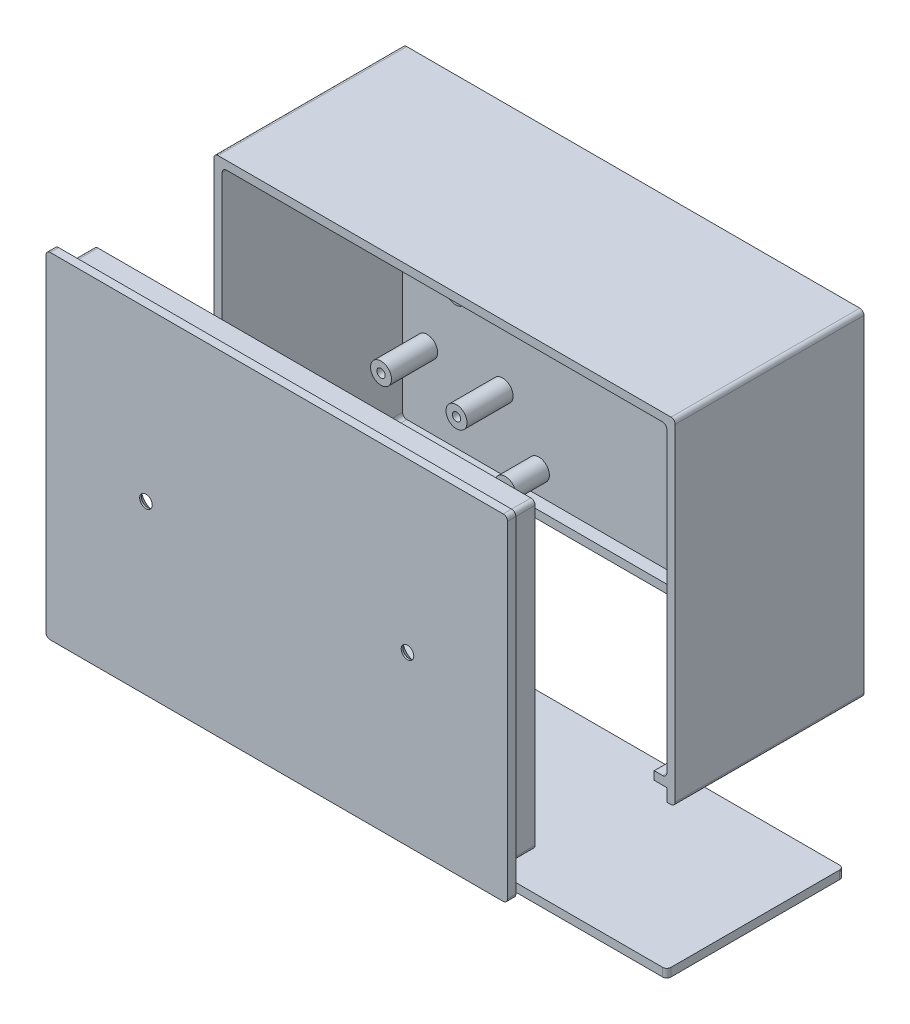
SolidWorks part; units mm, degrees
ref_plane "Спереди" through (0, 0, 0) normal (0, 0, 1) x (1, 0, 0)
ref_plane "Сверху" through (0, 0, 0) normal (0, 1, 0) x (1, 0, 0)
ref_plane "Справа" through (0, 0, 0) normal (1, 0, 0) x (0, 0, -1)
sketch "Эскиз1" plane through (0, 0, 0) normal (0, 0, 1) x (1, 0, 0)
  line L0 (-55, -41.511) -> (-53, -41.511)
  line L2 (-55, 38.489) -> (-55, -41.511)
  line L5 (-55, 38.489) -> (55, 38.489)
  line L6 (53, -36.511) -> (53, 36.489)
  line L7 (-53, -41.511) -> (-53, -38.511)
  line L8 (-53, -38.511) -> (-50, -38.511)
  line L9 (-50, -38.511) -> (-50, -36.511)
  line L10 (-50, -36.511) -> (-53, -36.511)
  line L11 (-53, -36.511) -> (-53, 36.489)
  line L12 (-53, 36.489) -> (53, 36.489)
  line L13 (0, 55.7111) -> (0, -96.3987) construction
  line L14 (50, -36.511) -> (53, -36.511)
  line L15 (50, -38.511) -> (50, -36.511)
  line L16 (53, -38.511) -> (50, -38.511)
  line L17 (53, -41.511) -> (53, -38.511)
  line L18 (55, 38.489) -> (55, -41.511)
  line L19 (55, -41.511) -> (53, -41.511)
  point P0 (0, 0)
  point P15 (0, 36.489)
  point P21 (0, 38.489)
  dimension "D1" = 2
  dimension "D2" = 2
  dimension "D3" = 2
  dimension "D4" = 55
  dimension "D5" = 80
  dimension "D6" = 2
  dimension "D7" = 3
  dimension "D8" = 3
extrude "Бобышка-Вытянуть3" add sketch "Эскиз1" along normal blind 43
sketch "Эскиз2" plane through (0, 0, 0) normal (0, 0, -1) x (-1, 0, 0)
  line L36 (55, 38.489) -> (55, -41.511) construction
  line L37 (-55, 38.489) -> (55, 38.489) construction
  line L38 (-55, -41.511) -> (-55, 38.489) construction
  line L39 (55, 38.489) -> (55, -41.511)
  line L40 (-55, 38.489) -> (55, 38.489)
  line L41 (-55, -41.511) -> (-55, 38.489)
  line L42 (-55, -41.511) -> (55, -41.511)
extrude "Бобышка-Вытянуть4" add sketch "Эскиз2" along normal blind 2
ref_plane "Плоскость1" through (0, 0, 8) normal (0, 0, 1) x (1, 0, 0)
sketch "Эскиз3" plane through (0, 0, 8) normal (0, 0, 1) x (1, 0, 0)
  line L0 (-53, -38.511) -> (-50, -38.511) construction
  line L1 (48, -32.511) -> (-23, -32.511) construction
  line L2 (48, -32.511) -> (48, 17.489) construction
  line L3 (48, 17.489) -> (-23, 17.489) construction
  line L4 (-23, -32.511) -> (-23, 17.489) construction
  line L5 (-33.1063, -7.511) -> (53.7568, -7.511) construction
  line L6 (12.5, 27.0434) -> (12.5, -35.2357) construction
  line L8 (50, -38.511) -> (53, -38.511) construction
  line L9 (53, 36.489) -> (53, -36.511) construction
  line L10 (-38.1409, 10.489) -> (-38.1409, -27.511) construction
  line L11 (-49.1409, 10.489) -> (-27.1409, 10.489) construction
  line L12 (-49.1409, 10.489) -> (-49.1409, -27.511) construction
  line L13 (-49.1409, -27.511) -> (-27.1409, -27.511) construction
  line L14 (-27.1409, 10.489) -> (-27.1409, -27.511) construction
  circle A0 centre (-20.5, 15.989) radius 1
  circle A1 centre (-20.5, 15.989) radius 2.5
  circle A2 centre (45.5, 15.989) radius 2.5
  circle A3 centre (45.5, 15.989) radius 1
  circle A4 centre (-20.5, 15.989) radius 1
  circle A5 centre (-20.5, 15.989) radius 2.5
  circle A6 centre (45.5, 15.989) radius 2.5
  circle A7 centre (45.5, 15.989) radius 1
  circle A8 centre (45.5, -31.011) radius 1
  circle A9 centre (45.5, -31.011) radius 2.5
  circle A10 centre (-20.5, -31.011) radius 2.5
  circle A11 centre (-20.5, -31.011) radius 1
  circle A12 centre (45.5, -31.011) radius 1
  circle A13 centre (45.5, -31.011) radius 2.5
  circle A14 centre (-20.5, -31.011) radius 2.5
  circle A15 centre (-20.5, -31.011) radius 1
  circle A16 centre (-47.1409, -19.011) radius 1
  circle A17 centre (-47.1409, -19.011) radius 2.5
  circle A18 centre (-29.1409, -19.011) radius 2.5
  circle A19 centre (-29.1409, -19.011) radius 1
  circle A20 centre (-29.3409, 6.489) radius 2.5
  circle A21 centre (-29.3409, 6.489) radius 1
  point P0 (12.5, -7.511)
  point P35 (12.5, 17.489)
  point P36 (-23, -7.511)
  point P40 (-38.1409, -8.8408)
  point P51 (0, 0)
  point P52 (0, 0)
  point P53 (-27.3853, 3.4956)
  point P54 (0, 0)
  point P55 (0, 0)
  point P56 (0, 0)
  point P57 (0, 0)
  point P59 (0, 0)
  dimension "D5" = 2
  dimension "D6" = 5
  dimension "D11" = 2
  dimension "D12" = 5
  dimension "D1" = 50
  dimension "D2" = 71
  dimension "D3" = 6
  dimension "D4" = 5
  dimension "D7" = 47
  dimension "D8" = 66
  dimension "D9" = 38
  dimension "D10" = 22
  dimension "D13" = 8.5
  dimension "D14" = 18
  dimension "D15" = 4
  dimension "D16" = 2.2
  dimension "D17" = 11
extrude "Бобышка-Вытянуть2" add sketch "Эскиз3" against normal up to surface (8 mm away) contours A1 | A10 | A11 | A2 | A3 | A9 | A8 | A0 up to face at (0, -25.8443, 0)
sketch "Эскиз4" plane through (0, 0, 0) normal (0, 0, 1) x (1, 0, 0)
  line L0 (-50, -36.511) -> (-50, -38.511)
  line L1 (-50, -38.511) -> (50, -38.511)
  line L2 (50, -38.511) -> (50, -36.511)
  line L3 (50, -36.511) -> (-50, -36.511)
extrude "Бобышка-Вытянуть5" add sketch "Эскиз4" along normal blind 3
ref_plane "Плоскость2" through (0, 0, 83) normal (0, 0, 1) x (1, 0, 0)
sketch "Эскиз5" plane through (0, 0, 83) normal (0, 0, 1) x (1, 0, 0)
  line L0 (55, -41.511) -> (55, 38.489) construction
  line L1 (55, 38.489) -> (-55, 38.489) construction
  line L2 (-55, 38.489) -> (-55, -41.511) construction
  line L3 (55, -41.511) -> (55, 38.489)
  line L4 (55, 38.489) -> (-55, 38.489)
  line L5 (-55, 38.489) -> (-55, -41.511)
  line L6 (-55, -41.511) -> (55, -41.511)
  line L7 (-55, -1.511) -> (66.1555, -1.511) construction
  line L8 (0, 36.489) -> (0, -47.4003) construction
  line L9 (-53, 36.489) -> (53, 36.489) construction
  circle A0 centre (-31.1737, -1.511) radius 1.5
  circle A1 centre (31.1737, -1.511) radius 1.5
  dimension "D1" = 3
extrude "Бобышка-Вытянуть6" add sketch "Эскиз5" against normal blind 2 separate body
sketch "Эскиз6" plane through (0, 0, 83) normal (0, 0, 1) x (1, 0, 0)
  line L0 (-50.6, 34.089) -> (50.6, 34.089)
  line L1 (50.6, 34.089) -> (50.6, -34.111)
  line L2 (50.6, -34.111) -> (50, -34.111)
  line L3 (0, 55.7111) -> (0, -96.3987) construction
  line L4 (50, -34.111) -> (50, -36.111)
  line L5 (49.6, -36.511) -> (49.6, -38.511)
  line L6 (-49.6, -38.511) -> (-49.6, -36.511)
  line L24 (-50, -36.111) -> (-50, -34.111)
  line L25 (-50, -34.111) -> (-50.6, -34.111)
  line L26 (-50.6, -34.111) -> (-50.6, 34.089)
  line L31 (52.6, -36.111) -> (50, -36.111)
  line L32 (52.6, 36.089) -> (52.6, -36.111)
  line L33 (-52.6, 36.089) -> (52.6, 36.089)
  line L34 (49.6, -36.511) -> (-49.6, -36.511)
  line L35 (-49.6, -38.511) -> (49.6, -38.511)
  line L36 (-52.6, -36.111) -> (-52.6, 36.089)
  line L37 (-50, -36.111) -> (-52.6, -36.111)
  line L38 (52.6, -36.111) -> (50, -36.111)
  line L39 (52.6, 36.089) -> (52.6, -36.111)
  line L40 (-52.6, 36.089) -> (52.6, 36.089)
  line L41 (-52.6, -36.111) -> (-52.6, 36.089)
  line L42 (-50, -36.111) -> (-52.6, -36.111)
  point P0 (0, -38.511)
  dimension "D1" = 99.2
  dimension "D3" = 2
  dimension "D4" = 2
  dimension "D5" = 2
  dimension "D6" = 2
  dimension "D7" = 2
  dimension "D2" = 0.4
extrude "Бобышка-Вытянуть7" add sketch "Эскиз6" against normal blind 9 contours L42 L24 L25 L26 L0 L1 L2 L4 L38 L39 L40 L41 region at (-51.8759, -0.011, 83)
extrude "Бобышка-Вытянуть8" add sketch "Эскиз6<3>" against normal blind 5 contours L6 L35 L5 L34 region at (0, -37.511, 83)
sketch "Эскиз6<3>" plane through (0, 0, 83) normal (0, 0, 1) x (1, 0, 0) same geometry as "Эскиз6"
ref_plane "Плоскость3" through (0, -78.511, 0) normal (0, -1, 0) x (-1, 0, 0)
sketch "Эскиз10" plane through (0, -78.511, 0) normal (0, -1, 0) x (-1, 0, 0)
  line L4 (50, -43) -> (50, -3) construction
  line L5 (-50, -3) -> (50, -3) construction
  line L6 (-50, -3) -> (-50, -39.4) construction
  line L7 (-50, -39.4) -> (50, -39.4) construction
  line L8 (-52.6, -42.6) -> (52.6, -42.6)
  line L9 (52.6, -42.6) -> (52.6, -0.4)
  line L10 (52.6, -0.4) -> (-52.6, -0.4)
  line L11 (-52.6, -0.4) -> (-52.6, -42.6)
  line L12 (-52.6, -42.6) -> (52.6, -42.6)
  line L13 (52.6, -42.6) -> (52.6, -0.4)
  line L14 (52.6, -0.4) -> (-52.6, -0.4)
  line L15 (-52.6, -0.4) -> (-52.6, -42.6)
  line L16 (50, -3) -> (50, -39.4) construction
  line L17 (-50, -3) -> (50, -39.4) construction
  line L18 (-50, -39.4) -> (50, -3) construction
  point P4 (0, -21.2)
  dimension "D2" = 3.2
  dimension "D1" = 0.4
extrude "Бобышка-Вытянуть9" add sketch "Эскиз10" against normal blind 2 separate body
chamfer "Фаска1" distance 1.6 angle 45 2 edges at (29.6737, -1.511, 81) (-29.6737, -1.511, 81)
fillet "Скругление1" radius 1 8 edges at (-53, -36.511, 21.5) (-53, 36.489, 21.5) (53, 36.489, 21.5) (53, -36.511, 21.5) (-55, -41.511, 20.5) (55, -41.511, 20.5) (55, 38.489, 20.5) (-55, 38.489, 20.5)
fillet "Скругление2" radius 1 10 edges at (-55, -41.511, 82) (55, -41.511, 82) (55, 38.489, 82) (-55, 38.489, 82) (52.6, 36.089, 77.5) (50, -36.111, 77.5) (52.6, -36.111, 77.5) (-50, -36.111, 77.5) (-52.6, -36.111, 77.5) (-52.6, 36.089, 77.5)
fillet "Скругление3" radius 1 4 edges at (-52.6, -77.511, 0.4) (-52.6, -77.511, 42.6) (52.6, -77.511, 42.6) (52.6, -77.511, 0.4)
extrude "Бобышка-Вытянуть10" add sketch "Эскиз3<3>" against normal up to surface (10 mm away) from offset 3 contours A17 | A16 | A19 | A18 | A20 | A21 up to face at (0, -1.511, -2)
sketch "Эскиз3<3>" plane through (0, 0, 8) normal (0, 0, 1) x (1, 0, 0) same geometry as "Эскиз3"
equation "\"D5@Эскиз6\"=\"D4@Эскиз6\""
equation "\"D6@Эскиз6\"=\"D4@Эскиз6\""
equation "\"D7@Эскиз6\"=\"D4@Эскиз6\""
equation "\"D3@Эскиз6\"=\"D4@Эскиз6\""
